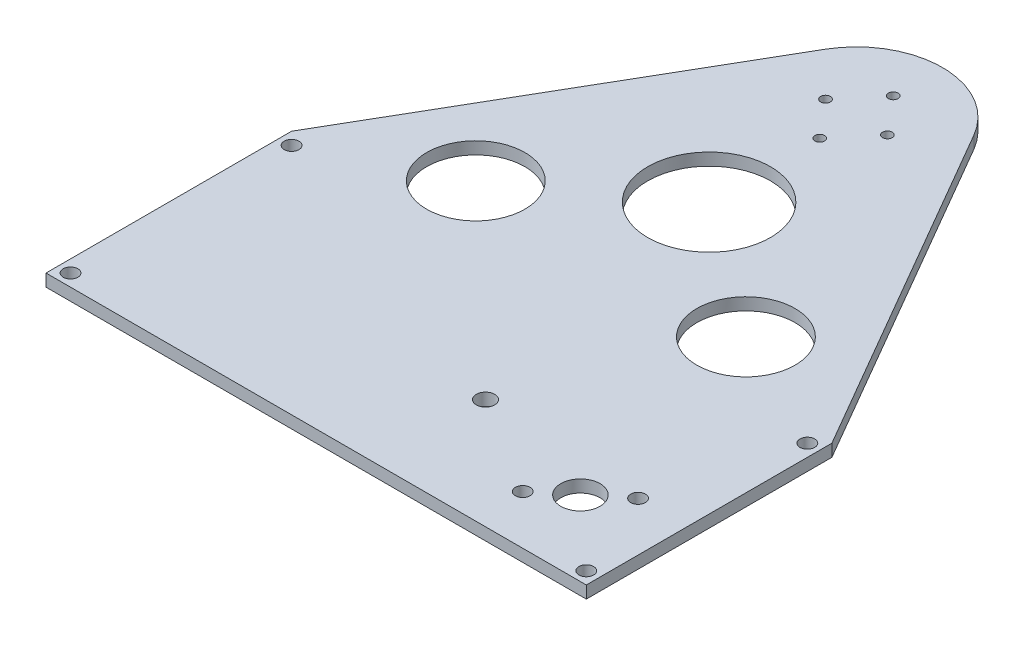
SolidWorks part; units mm, degrees
material "PLA/ABS"
ref_plane "Front Plane" through (0, 0, 0) normal (0, 0, 1) x (1, 0, 0)
ref_plane "Top Plane" through (0, 0, 0) normal (0, 1, 0) x (1, 0, 0)
ref_plane "Right Plane" through (0, 0, 0) normal (1, 0, 0) x (0, 0, -1)
other "Bounding Box"
ref_plane "Default Plane" through (-8.9266, -12.7485, 0) normal (-0.1736, 0.9848, 0) x (0.9848, 0.1736, 0)
sketch "Sketch1" plane through (0, 0, 0) normal (0, 1, 0) x (1, 0, 0)
  line L0 (0, 0) -> (0, -95.25) construction
  line L1 (0, -95.25) -> (-19.05, -95.25) construction
  line L2 (-76.2, -95.25) -> (-69.85, -95.25) construction
  line L3 (-69.85, -105.2195) -> (-19.05, -105.2195)
  line L4 (-69.85, -105.2195) -> (-69.85, -85.2805)
  line L5 (-69.85, -85.2805) -> (-19.05, -85.2805)
  line L6 (-19.05, -105.2195) -> (-19.05, -85.2805)
  line L7 (-69.85, -105.2195) -> (-19.05, -85.2805) construction
  line L8 (-69.85, -85.2805) -> (-19.05, -105.2195) construction
  line L9 (-88.9, -120.65) -> (-76.2, -120.65)
  line L10 (-88.9, -120.65) -> (-88.9, -69.85)
  line L11 (-88.9, -69.85) -> (-76.2, -69.85)
  line L12 (-76.2, -120.65) -> (-76.2, -69.85)
  line L13 (-88.9, -120.65) -> (-76.2, -69.85) construction
  line L14 (-88.9, -69.85) -> (-76.2, -120.65) construction
  line L15 (69.85, -85.2805) -> (19.05, -85.2805)
  line L16 (-63.5, -133.35) -> (-6.35, -133.35)
  line L17 (-63.5, -133.35) -> (-63.5, -116.84)
  line L18 (-63.5, -116.84) -> (-6.35, -116.84)
  line L19 (-6.35, -133.35) -> (-6.35, -116.84)
  line L20 (-63.5, -133.35) -> (-6.35, -116.84) construction
  line L21 (-63.5, -116.84) -> (-6.35, -133.35) construction
  line L22 (19.05, -105.2195) -> (19.05, -85.2805)
  line L23 (69.85, -105.2195) -> (19.05, -105.2195)
  line L24 (69.85, -105.2195) -> (69.85, -85.2805)
  line L25 (88.9, -69.85) -> (76.2, -69.85)
  line L26 (76.2, -120.65) -> (76.2, -69.85)
  line L27 (88.9, -120.65) -> (76.2, -120.65)
  line L28 (88.9, -120.65) -> (88.9, -69.85)
  line L30 (63.5, -133.35) -> (20.32, -133.35)
  line L31 (63.5, -133.35) -> (63.5, -113.2078)
  line L32 (63.5, -113.2078) -> (20.32, -113.2078)
  line L33 (20.32, -133.35) -> (20.32, -113.2078)
  line L34 (63.5, -133.35) -> (20.32, -113.2078) construction
  line L35 (63.5, -113.2078) -> (20.32, -133.35) construction
  line L36 (-69.85, -139.7) -> (69.85, -139.7)
  line L37 (-69.85, -139.7) -> (-69.85, -76.2)
  line L38 (-69.85, -76.2) -> (69.85, -76.2)
  line L39 (69.85, -139.7) -> (69.85, -76.2)
  line L40 (-69.85, -139.7) -> (69.85, -76.2) construction
  line L41 (-69.85, -76.2) -> (69.85, -139.7) construction
  circle A0 centre (0, 0) radius 69.85
  circle A1 centre (0, 0) radius 13.843
  point P3 (-34.925, -125.095)
  point P6 (-44.45, -95.25)
  point P12 (-82.55, -95.25)
  point P22 (0, -76.2)
  point P23 (0, -107.95)
  point P36 (0, -69.85)
  point P38 (41.91, -123.2789)
  dimension "D1" = 139.7
  dimension "D19" = 27.686
  dimension "D2" = 50.8
  dimension "D3" = 19.939
  dimension "D4" = 50.8
  dimension "D5" = 12.7
  dimension "D6" = 57.15
  dimension "D7" = 16.51
  dimension "D8" = 43.18
  dimension "D9" = 20.1422
  dimension "D10" = 6.35
  dimension "D11" = 139.7
  dimension "D12" = 44.45
  dimension "D13" = 6.35
  dimension "D14" = 6.35
  dimension "D15" = 6.35
  dimension "D16" = 6.35
  dimension "D17" = 63.5
  dimension "D18" = 6.35
sketch "Sketch2" plane through (0, 0, 0) normal (1, 0, 0) x (0, 0, -1)
  line L1 (-139.7, 12.7) -> (-76.2, 12.7)
  line L2 (-139.7, 12.7) -> (-139.7, -12.7)
  line L3 (-139.7, -12.7) -> (-76.2, -12.7)
  line L4 (-76.2, 12.7) -> (-76.2, -12.7)
  line L5 (-139.7, 12.7) -> (-76.2, -12.7) construction
  line L6 (-139.7, -12.7) -> (-76.2, 12.7) construction
  line L7 (-139.7, 12.7) -> (12.7, 12.7)
  line L8 (-139.7, 12.7) -> (-139.7, 15.875)
  line L9 (-139.7, 15.875) -> (12.7, 15.875)
  line L10 (12.7, 12.7) -> (12.7, 15.875)
  line L11 (-139.7, 12.7) -> (12.7, 15.875) construction
  line L12 (-139.7, 15.875) -> (12.7, 12.7) construction
  line L13 (-139.7, -12.7) -> (-76.2, -12.7)
  line L14 (-139.7, -12.7) -> (-139.7, -15.875)
  line L15 (-139.7, -15.875) -> (-76.2, -15.875)
  line L16 (-76.2, -12.7) -> (-76.2, -15.875)
  line L17 (-139.7, -12.7) -> (-76.2, -15.875) construction
  line L18 (-139.7, -15.875) -> (-76.2, -12.7) construction
  circle A0 centre (-95.25, 0) radius 25.4
  point P4 (-120.65, 0)
  point P5 (-107.95, 0)
  point P15 (-63.5, 14.2875)
  point P19 (-107.95, -14.2875)
  dimension "D1" = 25.4
  dimension "D2" = 3.175
  dimension "D3" = 12.7
sketch "Sketch3" plane through (0, 0, 0) normal (0, 1, 0) x (1, 0, 0)
  line L1 (-69.85, -139.7) -> (69.85, -139.7)
  line L2 (-69.85, -139.7) -> (-69.85, -76.2)
  line L3 (-69.85, -76.2) -> (69.85, -76.2)
  line L4 (69.85, -139.7) -> (69.85, -76.2)
  line L5 (-69.85, -139.7) -> (69.85, -76.2) construction
  line L6 (-69.85, -76.2) -> (69.85, -139.7) construction
  line L7 (-63.5, -82.55) -> (63.5, -82.55)
  line L8 (-63.5, -82.55) -> (-63.5, -133.35)
  line L9 (-63.5, -133.35) -> (63.5, -133.35)
  line L10 (63.5, -82.55) -> (63.5, -133.35)
  line L11 (-63.5, -82.55) -> (63.5, -133.35) construction
  line L12 (-63.5, -133.35) -> (63.5, -82.55) construction
  point P0 (0, -107.95)
  point P7 (0, -107.95)
extrude "Boss-Extrude1" add sketch "Sketch3" along normal up to vertex (12.7 mm away) and the other way up to vertex (12.7 mm away) up to point (0, 12.7, 139.7) other way up to point (0, -12.7, 139.7)
sketch "Sketch4" plane through (0, -12.7, 0) normal (0, -1, 0) x (1, 0, 0)
  line L1 (-69.85, 139.7) -> (69.85, 139.7)
  line L2 (-69.85, 139.7) -> (-69.85, 76.2)
  line L3 (-69.85, 76.2) -> (69.85, 76.2)
  line L4 (69.85, 139.7) -> (69.85, 76.2)
  line L5 (-69.85, 139.7) -> (69.85, 76.2) construction
  line L6 (-69.85, 76.2) -> (69.85, 139.7) construction
  point P0 (0, 107.95)
extrude "Boss-Extrude2" add sketch "Sketch4" along normal up to vertex (3.175 mm away) up to point (0, -15.875, 139.7)
sketch "Sketch5" plane through (0, 12.7, 0) normal (0, 1, 0) x (1, 0, 0)
  line L0 (-19.229, 11.1443) -> (-69.85, -76.2)
  line L1 (-69.85, -76.2) -> (-69.85, -139.7)
  line L2 (-69.85, -139.7) -> (69.85, -139.7)
  line L3 (69.85, -139.7) -> (69.85, -76.2)
  line L4 (69.85, -76.2) -> (19.229, 11.1443)
  arc A0 (-19.229, 11.1443) -> (19.229, 11.1443) centre (0, 0) cw
  dimension "D1" = 22.225
extrude "Boss-Extrude3" add sketch "Sketch5" along normal up to vertex (3.175 mm away) separate body up to point (0, 15.875, 139.7)
sketch "Sketch7" plane through (0, -12.7, 0) normal (0, 1, 0) x (1, 0, 0)
  line L0 (-19.05, -105.2195) -> (-19.05, -85.2805) construction
  line L1 (-63.5, -82.55) -> (-19.05, -82.55)
  line L2 (-63.5, -82.55) -> (-63.5, -107.95)
  line L3 (-63.5, -107.95) -> (-19.05, -107.95)
  line L4 (-19.05, -82.55) -> (-19.05, -107.95)
  line L5 (-63.5, -82.55) -> (-19.05, -107.95) construction
  line L6 (-63.5, -107.95) -> (-19.05, -82.55) construction
  line L7 (63.5, -82.55) -> (19.05, -82.55)
  line L8 (63.5, -82.55) -> (63.5, -107.95)
  line L9 (63.5, -107.95) -> (19.05, -107.95)
  line L10 (19.05, -82.55) -> (19.05, -107.95)
  line L11 (63.5, -82.55) -> (19.05, -107.95) construction
  line L12 (63.5, -107.95) -> (19.05, -82.55) construction
  line L13 (19.05, -105.2195) -> (19.05, -85.2805) construction
  line L14 (0, -95.25) -> (-19.05, -95.25) construction
  point P4 (-41.275, -95.25)
  point P10 (41.275, -95.25)
extrude "Boss-Extrude4" add sketch "Sketch7" along normal blind 6.35
sketch "Sketch6" plane through (-69.85, 0, 0) normal (-1, 0, 0) x (0, 0, 1)
  circle A0 centre (95.25, 0) radius 9.9695
extrude "Cut-Extrude1" cut sketch "Sketch6" against normal through all
ref_plane "Plane1" through (0, 0, 0) normal (1, 0, 0) x (0, 0, -1)
sketch "Sketch9" plane through (0, 0, 0) normal (1, 0, 0) x (0, 0, -1)
  line L0 (-139.7, 0) -> (-139.7, 5.08)
  line L1 (-139.7, 12.7) -> (-139.7, -15.875) construction
  line L2 (-139.7, 5.08) -> (-152.4, 0)
  line L3 (-152.4, 0) -> (-139.7, 0)
  dimension "D1" = 12.7
  dimension "D2" = 5.08
revolve "Revolve1" add sketch "Sketch9" angle 360 about L3
pattern_linear "LPattern1" count 3 spacing 25.4 along (-1, 0, 0) count 3 spacing 25.4 along (1, 0, 0) of "Revolve1"
sketch "Sketch13" plane through (0, -12.7, 0) normal (0, 1, 0) x (1, 0, 0)
  line L0 (-63.5, -107.95) -> (-19.05, -107.95) construction
  line L1 (-19.05, -82.55) -> (-48.26, -82.55)
  line L2 (-19.05, -82.55) -> (-19.05, -107.95)
  line L3 (-19.05, -107.95) -> (-48.26, -107.95)
  line L4 (-48.26, -82.55) -> (-48.26, -107.95)
  line L5 (-19.05, -82.55) -> (-48.26, -107.95) construction
  line L6 (-19.05, -107.95) -> (-48.26, -82.55) construction
  line L7 (-63.5, -82.55) -> (-63.5, -87.5644) construction
  line L9 (0, -17.4625) -> (0, 17.4625) construction
  line L10 (48.26, -82.55) -> (48.26, -107.95)
  line L11 (19.05, -107.95) -> (48.26, -107.95)
  line L12 (19.05, -82.55) -> (19.05, -107.95)
  line L13 (19.05, -82.55) -> (48.26, -82.55)
  point P4 (-33.655, -95.25)
  dimension "D1" = 15.24
extrude "Boss-Extrude5" add sketch "Sketch13" along normal blind 4.064
sketch "Sketch14" plane through (0, 0, 107.95) normal (0, 0, 1) x (1, 0, 0)
  line L0 (-48.26, -8.0762) -> (-48.26, -11.2291) construction
  line L1 (-43.18, -9.144) -> (-36.83, -9.144)
  line L2 (-43.18, -9.144) -> (-43.18, -11.684)
  line L3 (-43.18, -11.684) -> (-36.83, -11.684)
  line L4 (-36.83, -9.144) -> (-36.83, -11.684)
  line L5 (-43.18, -9.144) -> (-36.83, -11.684) construction
  line L6 (-43.18, -11.684) -> (-36.83, -9.144) construction
  line L7 (-48.26, -8.636) -> (-48.26, -9.9695) construction
  line L8 (-19.05, -6.35) -> (-63.5, -6.35) construction
  line L9 (-43.18, -5.08) -> (-36.83, -5.08)
  line L10 (-43.18, -5.08) -> (-43.18, -2.54)
  line L11 (-43.18, -2.54) -> (-36.83, -2.54)
  line L12 (-36.83, -5.08) -> (-36.83, -2.54)
  line L13 (-43.18, -5.08) -> (-36.83, -2.54) construction
  line L14 (-43.18, -2.54) -> (-36.83, -5.08) construction
  line L15 (-63.5, -12.7) -> (-19.05, -12.7) construction
  line L16 (0, -17.4625) -> (0, 17.4625) construction
  line L17 (43.18, -11.684) -> (36.83, -11.684)
  line L18 (36.83, -9.144) -> (36.83, -11.684)
  line L19 (43.18, -9.144) -> (36.83, -9.144)
  line L20 (43.18, -9.144) -> (43.18, -11.684)
  line L21 (43.18, -2.54) -> (36.83, -2.54)
  line L22 (36.83, -5.08) -> (36.83, -2.54)
  line L23 (43.18, -5.08) -> (36.83, -5.08)
  line L24 (43.18, -5.08) -> (43.18, -2.54)
  point P4 (-40.005, -10.414)
  point P13 (-40.005, -3.81)
  dimension "D1" = 2.54
  dimension "D2" = 6.35
  dimension "D3" = 5.08
  dimension "D4" = 1.27
  dimension "D5" = 1.016
extrude "Cut-Extrude2" cut sketch "Sketch14" against normal up to surface (31.75 mm away) up to face at (0, -1.5875, 76.2)
sketch "Sketch18" plane through (0, 0, 82.55) normal (0, 0, 1) x (1, 0, 0)
  line L0 (63.5, 12.7) -> (-63.5, 12.7) construction
  line L1 (-60.96, 12.7) -> (-50.8, 12.7)
  line L2 (-60.96, 12.7) -> (-60.96, 7.62)
  line L3 (-60.96, 7.62) -> (-50.8, 7.62)
  line L4 (-50.8, 12.7) -> (-50.8, 7.62)
  line L5 (-60.96, 12.7) -> (-50.8, 7.62) construction
  line L6 (-60.96, 7.62) -> (-50.8, 12.7) construction
  line L7 (-63.5, 12.7) -> (-63.5, -6.35) construction
  point P4 (-55.88, 10.16)
  dimension "D1" = 10.16
  dimension "D2" = 2.54
  dimension "D3" = 5.08
extrude "Cut-Extrude3" cut sketch "Sketch18" against normal up to surface (6.35 mm away) up to face at (-40.005, -3.81, 76.2)
sketch "Sketch19" plane through (0, 12.7, 0) normal (0, 1, 0) x (1, 0, 0)
  line L0 (-69.85, -76.2) -> (-69.85, -139.7) construction
  line L1 (-60.96, -76.2) -> (-69.85, -76.2) construction
  line L2 (-63.5, -82.55) -> (-63.5, -133.35) construction
  line L5 (69.85, -139.7) -> (69.85, -76.2) construction
  line L6 (69.85, -76.2) -> (-50.8, -76.2) construction
  line L7 (-69.85, -139.7) -> (69.85, -139.7) construction
  line L8 (-63.5, -133.35) -> (63.5, -133.35) construction
  circle A0 centre (-66.675, -79.375) radius 3.175 construction
  circle A1 centre (-66.675, -79.375) radius 0.635
  circle A2 centre (66.675, -79.375) radius 3.175 construction
  circle A3 centre (66.675, -79.375) radius 0.635
  circle A4 centre (-66.675, -136.525) radius 3.175 construction
  circle A5 centre (-66.675, -136.525) radius 0.635
  circle A6 centre (66.675, -136.525) radius 3.175 construction
  circle A7 centre (66.675, -136.525) radius 0.635
  dimension "D1" = 1.27
  dimension "D2" = 6.35
extrude "Cut-Extrude4" cut sketch "Sketch19" against normal blind 25.4
sketch "Sketch20" plane through (0, 15.875, 0) normal (0, 1, 0) x (1, 0, 0)
  circle A0 centre (-66.675, -79.375) radius 1.905
  circle A1 centre (-66.675, -136.525) radius 1.905
  circle A2 centre (66.675, -136.525) radius 1.905
  circle A3 centre (66.675, -79.375) radius 1.905
  dimension "D1" = 3.81
  dimension "D2" = 3.81
  dimension "D3" = 3.81
  dimension "D4" = 3.81
extrude "Cut-Extrude7" cut sketch "Sketch20" against normal up to surface (3.175 mm away) up to face at (0, 12.7, 66.4051)
sketch "Sketch23" plane through (0, 15.875, 0) normal (0, 1, 0) x (1, 0, 0)
  line L0 (-69.85, -139.7) -> (69.85, -139.7) construction
  line L1 (57.15, -113.6085) -> (40.715, -113.6085) construction
  line L2 (57.15, -113.6085) -> (57.15, -127) construction
  line L3 (57.15, -127) -> (40.715, -127) construction
  line L4 (40.715, -113.6085) -> (40.715, -127) construction
  line L5 (57.15, -113.6085) -> (40.715, -127) construction
  line L6 (57.15, -127) -> (40.715, -113.6085) construction
  line L7 (69.85, -139.7) -> (69.85, -76.2) construction
  circle A0 centre (48.9325, -120.3043) radius 5.08
  circle A1 centre (57.15, -113.6085) radius 1.905
  circle A2 centre (40.715, -127) radius 1.905
  circle A4 centre (15.315, -111.2273) radius 2.3812
  point P0 (48.9325, -120.3043)
  dimension "D1" = 10.16
  dimension "D2" = 3.81
  dimension "D3" = 10.6
  dimension "D4" = 12.7
  dimension "D7" = 4.7625
  dimension "D8" = 25.4
  dimension "D5" = 12.7
  dimension "D6" = 13.3915
extrude "Cut-Extrude8" cut sketch "Sketch23" against normal up to surface (3.175 mm away) up to face at (-66.675, 12.7, 77.47)
sketch "Sketch24" plane through (0, 15.875, 0) normal (0, 1, 0) x (1, 0, 0)
  circle A0 centre (0, 0) radius 8 construction
  circle A1 centre (0, 0) radius 9.5 construction
  circle A2 centre (0, 9.5) radius 1.25
  circle A3 centre (0, -9.5) radius 1.25
  circle A4 centre (-8, 0) radius 1.25
  circle A5 centre (8, 0) radius 1.25
  dimension "D1" = 19
  dimension "D2" = 16
  dimension "D3" = 2.5
  dimension "D4" = 2.5
  dimension "D5" = 2.5
  dimension "D6" = 2.5
extrude "Cut-Extrude9" cut sketch "Sketch24" against normal up to surface (3.175 mm away) up to face at (15.315, 12.7, 108.846)
sketch "Sketch25" plane through (0, 15.875, 0) normal (0, 1, 0) x (1, 0, 0)
  line L0 (-34.925, -63.5) -> (0, -38.1) construction
  line L1 (0, -38.1) -> (34.925, -63.5) construction
  line L2 (34.925, -63.5) -> (-34.925, -63.5) construction
  line L3 (0, -63.5) -> (0, 0) construction
  line L4 (-69.85, -76.2) -> (69.85, -76.2) construction
  circle A0 centre (0, -38.1) radius 15.875
  circle A1 centre (-34.925, -63.5) radius 12.7
  circle A2 centre (34.925, -63.5) radius 12.7
  arc A3 (19.229, 11.1443) -> (-19.229, 11.1443) centre (0, 0) ccw construction
  dimension "D1" = 31.75
  dimension "D2" = 25.4
  dimension "D3" = 69.85
extrude "Cut-Extrude10" cut sketch "Sketch25" against normal through all
delete or keep bodies "Body-Delete/Keep 1" type delete bodies bodies 114
